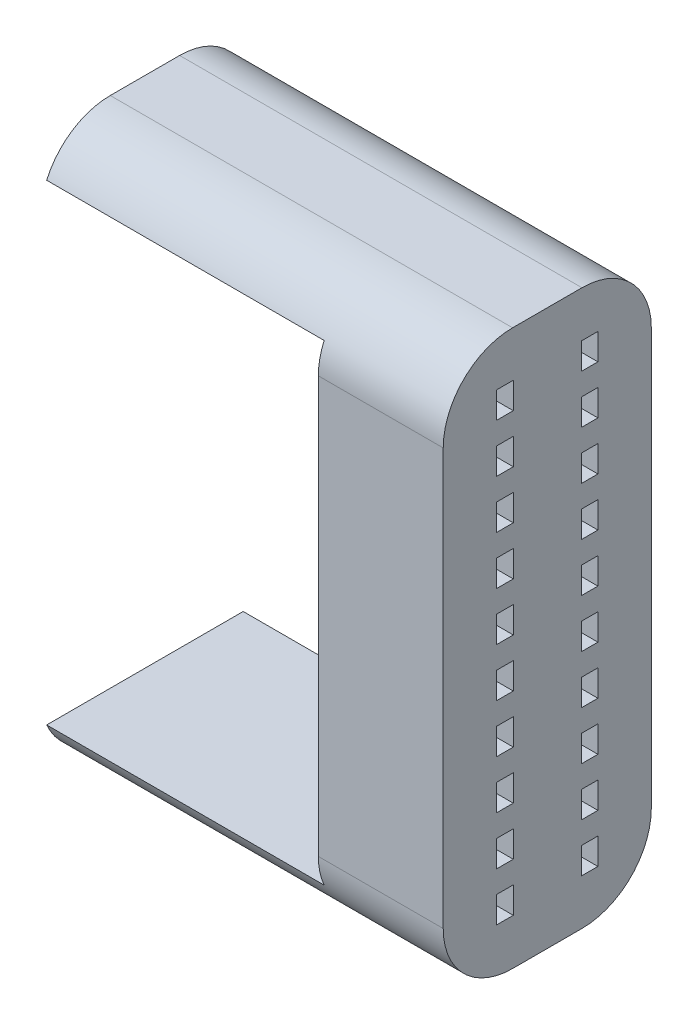
SolidWorks part; units mm, degrees
ref_plane "Front Plane" through (0, 0, 0) normal (1, 0, 0) x (0, 1, 0)
ref_plane "Top Plane" through (0, 0, 0) normal (0, 0, 1) x (0, 1, 0)
ref_plane "Right Plane" through (0, 0, 0) normal (0, 1, 0) x (-1, 0, 0)
sketch "Sketch1" plane through (0, 0, 0) normal (1, 0, 0) x (0, 1, 0)
  line L1 (-15, -7.5) -> (15, -7.5)
  line L2 (-20, -2.5) -> (-20, 2.5)
  line L3 (-15, 7.5) -> (15, 7.5)
  line L4 (20, -2.5) -> (20, 2.5)
  line L5 (-20, -7.5) -> (20, 7.5) construction
  line L6 (-20, 7.5) -> (20, -7.5) construction
  arc A0 (20, -2.5) -> (15, -7.5) centre (15, -2.5) cw
  arc A1 (-15, -7.5) -> (-20, -2.5) centre (-15, -2.5) cw
  arc A2 (20, 2.5) -> (15, 7.5) centre (15, 2.5) ccw
  arc A3 (-15, 7.5) -> (-20, 2.5) centre (-15, 2.5) ccw
  point P0 (0, 0)
  dimension "D3" = 5
  dimension "D1" = 40
  dimension "D2" = 15
extrude "Boss-Extrude1" add sketch "Sketch1" along normal blind 9
sketch "Sketch2" plane through (9, 0, 0) normal (1, 0, 0) x (0, 1, 0)
  line L0 (-11.3, 3.65) -> (-11.3, 2.45)
  line L1 (-16.7, 3.65) -> (-14.8, 3.65)
  line L2 (-16.7, 3.65) -> (-16.7, 2.45)
  line L3 (-16.7, 2.45) -> (-14.8, 2.45)
  line L4 (-14.8, 3.65) -> (-14.8, 2.45)
  line L5 (-13.2, 2.45) -> (-11.3, 2.45)
  line L6 (-13.2, 3.65) -> (-13.2, 2.45)
  line L7 (-13.2, 3.65) -> (-11.3, 3.65)
  line L8 (-7.8, 3.65) -> (-7.8, 2.45)
  line L9 (-9.7, 2.45) -> (-7.8, 2.45)
  line L10 (-9.7, 3.65) -> (-9.7, 2.45)
  line L11 (-9.7, 3.65) -> (-7.8, 3.65)
  line L12 (-4.3, 3.65) -> (-4.3, 2.45)
  line L13 (-6.2, 2.45) -> (-4.3, 2.45)
  line L14 (-6.2, 3.65) -> (-6.2, 2.45)
  line L15 (-6.2, 3.65) -> (-4.3, 3.65)
  line L16 (-0.8, 3.65) -> (-0.8, 2.45)
  line L17 (-2.7, 2.45) -> (-0.8, 2.45)
  line L18 (-2.7, 3.65) -> (-2.7, 2.45)
  line L19 (-2.7, 3.65) -> (-0.8, 3.65)
  line L20 (2.7, 3.65) -> (2.7, 2.45)
  line L21 (0.8, 2.45) -> (2.7, 2.45)
  line L22 (0.8, 3.65) -> (0.8, 2.45)
  line L23 (0.8, 3.65) -> (2.7, 3.65)
  line L24 (6.2, 3.65) -> (6.2, 2.45)
  line L25 (4.3, 2.45) -> (6.2, 2.45)
  line L26 (4.3, 3.65) -> (4.3, 2.45)
  line L27 (4.3, 3.65) -> (6.2, 3.65)
  line L28 (9.7, 3.65) -> (9.7, 2.45)
  line L29 (7.8, 2.45) -> (9.7, 2.45)
  line L30 (7.8, 3.65) -> (7.8, 2.45)
  line L31 (7.8, 3.65) -> (9.7, 3.65)
  line L32 (13.2, 3.65) -> (13.2, 2.45)
  line L33 (11.3, 2.45) -> (13.2, 2.45)
  line L34 (11.3, 3.65) -> (11.3, 2.45)
  line L35 (11.3, 3.65) -> (13.2, 3.65)
  line L36 (16.7, 3.65) -> (16.7, 2.45)
  line L37 (14.8, 2.45) -> (16.7, 2.45)
  line L38 (14.8, 3.65) -> (14.8, 2.45)
  line L39 (14.8, 3.65) -> (16.7, 3.65)
  line L40 (-11.3, -2.45) -> (-11.3, -3.65)
  line L41 (-13.2, -3.65) -> (-11.3, -3.65)
  line L42 (-13.2, -2.45) -> (-13.2, -3.65)
  line L43 (-13.2, -2.45) -> (-11.3, -2.45)
  line L44 (-7.8, -2.45) -> (-7.8, -3.65)
  line L45 (-9.7, -3.65) -> (-7.8, -3.65)
  line L46 (-9.7, -2.45) -> (-9.7, -3.65)
  line L47 (-9.7, -2.45) -> (-7.8, -2.45)
  line L48 (-4.3, -2.45) -> (-4.3, -3.65)
  line L49 (-6.2, -3.65) -> (-4.3, -3.65)
  line L50 (-6.2, -2.45) -> (-6.2, -3.65)
  line L51 (-6.2, -2.45) -> (-4.3, -2.45)
  line L52 (-0.8, -2.45) -> (-0.8, -3.65)
  line L53 (-2.7, -3.65) -> (-0.8, -3.65)
  line L54 (-2.7, -2.45) -> (-2.7, -3.65)
  line L55 (-2.7, -2.45) -> (-0.8, -2.45)
  line L56 (2.7, -2.45) -> (2.7, -3.65)
  line L57 (0.8, -3.65) -> (2.7, -3.65)
  line L58 (0.8, -2.45) -> (0.8, -3.65)
  line L59 (0.8, -2.45) -> (2.7, -2.45)
  line L60 (6.2, -2.45) -> (6.2, -3.65)
  line L61 (4.3, -3.65) -> (6.2, -3.65)
  line L62 (4.3, -2.45) -> (4.3, -3.65)
  line L63 (4.3, -2.45) -> (6.2, -2.45)
  line L64 (9.7, -2.45) -> (9.7, -3.65)
  line L65 (7.8, -3.65) -> (9.7, -3.65)
  line L66 (7.8, -2.45) -> (7.8, -3.65)
  line L67 (7.8, -2.45) -> (9.7, -2.45)
  line L68 (13.2, -2.45) -> (13.2, -3.65)
  line L69 (11.3, -3.65) -> (13.2, -3.65)
  line L70 (11.3, -2.45) -> (11.3, -3.65)
  line L71 (11.3, -2.45) -> (13.2, -2.45)
  line L72 (16.7, -2.45) -> (16.7, -3.65)
  line L73 (14.8, -3.65) -> (16.7, -3.65)
  line L74 (14.8, -2.45) -> (14.8, -3.65)
  line L75 (14.8, -2.45) -> (16.7, -2.45)
  line L76 (-14.8, -2.45) -> (-14.8, -3.65)
  line L77 (-16.7, -3.65) -> (-14.8, -3.65)
  line L78 (-16.7, -2.45) -> (-16.7, -3.65)
  line L79 (-16.7, -2.45) -> (-14.8, -2.45)
  line L80 (0, 7.5) -> (0, -7.5) construction
  line L81 (15, 7.5) -> (-15, 7.5) construction
  line L82 (-15, -7.5) -> (15, -7.5) construction
  line L83 (-15.75, 2.45) -> (-15.75, -2.45) construction
  line L84 (15.75, 2.45) -> (15.75, -2.45) construction
  line L85 (-15.75, 0) -> (15.75, 0) construction
  line L86 (-15.75, 3.65) -> (-15.75, 2.45) construction
  line L87 (-12.25, 3.65) -> (-12.25, 2.45) construction
  line L88 (-15.75, -2.45) -> (-15.75, -3.65) construction
  line L89 (-12.25, -2.45) -> (-12.25, -3.65) construction
  line L90 (-12.25, -3.05) -> (-15.75, -3.05) construction
  line L91 (-12.25, 3.05) -> (-15.75, 3.05) construction
  dimension "D1" = 1.9
  dimension "D2" = 1.2
  dimension "D5" = 3.5
  dimension "D6" = 6.1
  dimension "D3" = 10
  dimension "D4" = 2
extrude "Cut-Extrude1" cut sketch "Sketch2" against normal through all
sketch "Sketch3" plane through (0, 0, 0) normal (-1, 0, 0) x (0, -1, 0)
  line L0 (-16.7, 2.45) -> (-14.8, 2.45)
  line L1 (-14.8, 2.45) -> (-14.8, 1.85)
  line L2 (-14.8, 1.85) -> (-16.7, 1.85)
  line L3 (-16.7, 1.85) -> (-16.7, 2.45)
  line L5 (-13.2, 2.45) -> (-11.3, 2.45)
  line L6 (-11.3, 2.45) -> (-11.3, 1.85)
  line L7 (-11.3, 1.85) -> (-13.2, 1.85)
  line L8 (-13.2, 1.85) -> (-13.2, 2.45)
  line L9 (-9.7, 2.45) -> (-7.8, 2.45)
  line L10 (-7.8, 2.45) -> (-7.8, 1.85)
  line L11 (-7.8, 1.85) -> (-9.7, 1.85)
  line L12 (-9.7, 1.85) -> (-9.7, 2.45)
  line L13 (-6.2, 2.45) -> (-4.3, 2.45)
  line L14 (-4.3, 2.45) -> (-4.3, 1.85)
  line L15 (-4.3, 1.85) -> (-6.2, 1.85)
  line L16 (-6.2, 1.85) -> (-6.2, 2.45)
  line L17 (-2.7, 2.45) -> (-0.8, 2.45)
  line L18 (-0.8, 2.45) -> (-0.8, 1.85)
  line L19 (-0.8, 1.85) -> (-2.7, 1.85)
  line L20 (-2.7, 1.85) -> (-2.7, 2.45)
  line L21 (0.8, 2.45) -> (2.7, 2.45)
  line L22 (2.7, 2.45) -> (2.7, 1.85)
  line L23 (2.7, 1.85) -> (0.8, 1.85)
  line L24 (0.8, 1.85) -> (0.8, 2.45)
  line L25 (4.3, 2.45) -> (6.2, 2.45)
  line L26 (6.2, 2.45) -> (6.2, 1.85)
  line L27 (6.2, 1.85) -> (4.3, 1.85)
  line L28 (4.3, 1.85) -> (4.3, 2.45)
  line L29 (7.8, 2.45) -> (9.7, 2.45)
  line L30 (9.7, 2.45) -> (9.7, 1.85)
  line L31 (9.7, 1.85) -> (7.8, 1.85)
  line L32 (7.8, 1.85) -> (7.8, 2.45)
  line L33 (11.3, 2.45) -> (13.2, 2.45)
  line L34 (13.2, 2.45) -> (13.2, 1.85)
  line L35 (13.2, 1.85) -> (11.3, 1.85)
  line L36 (11.3, 1.85) -> (11.3, 2.45)
  line L37 (14.8, 2.45) -> (16.7, 2.45)
  line L38 (16.7, 2.45) -> (16.7, 1.85)
  line L39 (16.7, 1.85) -> (14.8, 1.85)
  line L40 (14.8, 1.85) -> (14.8, 2.45)
  line L41 (-16.7, -3.65) -> (-14.8, -3.65)
  line L42 (-14.8, -3.65) -> (-14.8, -4.25)
  line L43 (-14.8, -4.25) -> (-16.7, -4.25)
  line L44 (-16.7, -4.25) -> (-16.7, -3.65)
  line L46 (-13.2, -3.65) -> (-11.3, -3.65)
  line L47 (-11.3, -3.65) -> (-11.3, -4.25)
  line L48 (-11.3, -4.25) -> (-13.2, -4.25)
  line L49 (-13.2, -4.25) -> (-13.2, -3.65)
  line L50 (-9.7, -3.65) -> (-7.8, -3.65)
  line L51 (-7.8, -3.65) -> (-7.8, -4.25)
  line L52 (-7.8, -4.25) -> (-9.7, -4.25)
  line L53 (-9.7, -4.25) -> (-9.7, -3.65)
  line L54 (-6.2, -3.65) -> (-4.3, -3.65)
  line L55 (-4.3, -3.65) -> (-4.3, -4.25)
  line L56 (-4.3, -4.25) -> (-6.2, -4.25)
  line L57 (-6.2, -4.25) -> (-6.2, -3.65)
  line L58 (-2.7, -3.65) -> (-0.8, -3.65)
  line L59 (-0.8, -3.65) -> (-0.8, -4.25)
  line L60 (-0.8, -4.25) -> (-2.7, -4.25)
  line L61 (-2.7, -4.25) -> (-2.7, -3.65)
  line L62 (0.8, -3.65) -> (2.7, -3.65)
  line L63 (2.7, -3.65) -> (2.7, -4.25)
  line L64 (2.7, -4.25) -> (0.8, -4.25)
  line L65 (0.8, -4.25) -> (0.8, -3.65)
  line L66 (4.3, -3.65) -> (6.2, -3.65)
  line L67 (6.2, -3.65) -> (6.2, -4.25)
  line L68 (6.2, -4.25) -> (4.3, -4.25)
  line L69 (4.3, -4.25) -> (4.3, -3.65)
  line L70 (7.8, -3.65) -> (9.7, -3.65)
  line L71 (9.7, -3.65) -> (9.7, -4.25)
  line L72 (9.7, -4.25) -> (7.8, -4.25)
  line L73 (7.8, -4.25) -> (7.8, -3.65)
  line L74 (11.3, -3.65) -> (13.2, -3.65)
  line L75 (13.2, -3.65) -> (13.2, -4.25)
  line L76 (13.2, -4.25) -> (11.3, -4.25)
  line L77 (11.3, -4.25) -> (11.3, -3.65)
  line L78 (14.8, -3.65) -> (16.7, -3.65)
  line L79 (16.7, -3.65) -> (16.7, -4.25)
  line L80 (16.7, -4.25) -> (14.8, -4.25)
  line L81 (14.8, -4.25) -> (14.8, -3.65)
  point P8 (-15.75, 1.85)
  point P9 (-12.25, 1.85)
  point P54 (-15.75, -4.25)
  point P91 (-12.25, -4.25)
  dimension "D2" = 3.5
  dimension "D4" = 3.5
  dimension "D5" = 0.6
  dimension "D1" = 10
  dimension "D3" = 10
extrude "Cut-Extrude2" cut sketch "Sketch3" against normal offset from surface (7 mm away) 2 up to face at (9, -5.25, -3.05)
sketch "Sketch4" plane through (0, 0, 0) normal (-1, 0, 0) x (0, -1, 0)
  line L0 (-17, 7.0826) -> (-17, -7.0826)
  line L1 (0, 7.5) -> (0, -7.5) construction
  line L2 (-15, 7.5) -> (15, 7.5) construction
  line L3 (15, -7.5) -> (-15, -7.5) construction
  line L4 (20, -2.5) -> (20, 2.5)
  line L6 (-20, -2.5) -> (-20, 2.5) construction
  line L7 (-20, -2.5) -> (-20, 2.5)
  line L8 (17, 7.0826) -> (17, -7.0826)
  arc A0 (-15, 7.5) -> (-20, 2.5) centre (-15, 2.5) ccw construction
  arc A1 (-20, -2.5) -> (-15, -7.5) centre (-15, -2.5) ccw construction
  arc A2 (-20, -2.5) -> (-17, -7.0826) centre (-15, -2.5) ccw
  arc A3 (-17, 7.0826) -> (-20, 2.5) centre (-15, 2.5) ccw
  arc A4 (17, 7.0826) -> (20, 2.5) centre (15, 2.5) cw
  arc A5 (20, -2.5) -> (17, -7.0826) centre (15, -2.5) cw
  dimension "D1" = 3
extrude "Boss-Extrude2" add sketch "Sketch4" along normal blind 20
sketch "Sketch5" plane through (0, -14.8, 0) normal (0, -1, 0) x (1, 0, 0)
  line L0 (0, -2.15) -> (9, -2.15) construction
  line L1 (0, 3.95) -> (9, 3.95) construction
  line L2 (0, -7.0826) -> (0, 7.0826) construction
  line L3 (9, 2.5) -> (9, 7.5) construction
  line L4 (9, -2.5) -> (9, 2.5) construction
  line L5 (0, -2.45) -> (9, -2.45) construction
  line L6 (0, 3.65) -> (9, 3.65) construction
  circle A0 centre (6, 3.95) radius 0.5
  circle A1 centre (2, 3.95) radius 0.5
  circle A2 centre (2, -2.15) radius 0.5
  circle A3 centre (6, -2.15) radius 0.5
  point P14 (2, 3.45)
  point P24 (2, -2.65)
  dimension "D1" = 1
  dimension "D2" = 0.2
  dimension "D3" = 4
  dimension "D4" = 3
  dimension "D5" = 0.2
extrude "Boss-Extrude3" add sketch "Sketch5" against normal up to surface and the other way up to surface up to face at (5.3333, 16.7, 2.65) other way up to face at (5.3333, -16.7, 2.65)
